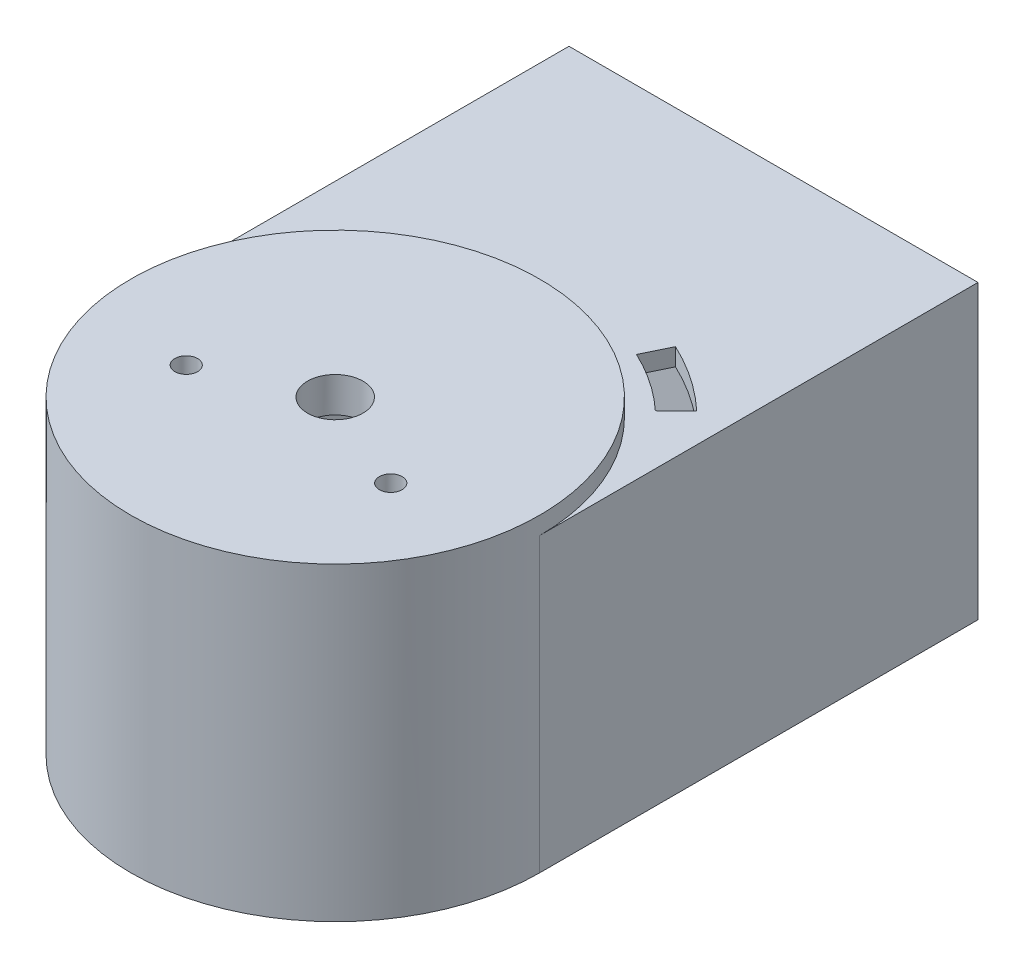
SolidWorks part; units mm, degrees
ref_plane "Alzado" through (0, 0, 0) normal (0, 0, 1) x (1, 0, 0)
ref_plane "Planta" through (0, 0, 0) normal (0, 1, 0) x (1, 0, 0)
ref_plane "Vista lateral" through (0, 0, 0) normal (1, 0, 0) x (0, 0, -1)
sketch "Croquis1" plane through (0, 0, 0) normal (0, 1, 0) x (1, 0, 0)
  circle A0 centre (0, 0) radius 4.75
  circle A1 centre (0, 0) radius 35
  dimension "D1" = 9.5
  dimension "D2" = 70
extrude "Saliente-Extruir1" add sketch "Croquis1" along normal blind 0.0001 and the other way blind 3
sketch "Croquis2" plane through (0, -3, 0) normal (0, -1, 0) x (1, 0, 0)
  circle A0 centre (-17.5, 8) radius 1.95
  circle A1 centre (17.5, 8) radius 1.95
  dimension "D4" = 3.9
  dimension "D1" = 8
  dimension "D2" = 35
  dimension "D3" = 17.5
extrude "Cortar-Extruir1" cut sketch "Croquis2" against normal through all
sketch "Croquis10" plane through (0, -3, 0) normal (0, -1, 0) x (1, 0, 0)
  line L1 (-35, 0) -> (-35, -75)
  line L2 (35, 0) -> (35, -75)
  line L3 (-35, -75) -> (35, -75)
  arc A0 (35, 0) -> (-35, 0) centre (0, 0) ccw
  circle A1 centre (0, 0) radius 4.75
  circle A2 centre (-17.5, 8) radius 1.95
  circle A3 centre (17.5, 8) radius 1.95
extrude "Saliente-Extruir3" add sketch "Croquis10" along normal blind 50
sketch "Croquis11" plane through (0, -53, 0) normal (0, -1, 0) x (1, 0, 0)
  line L1 (-32.0976, 0) -> (-32, -69.5)
  line L2 (32.0976, 0) -> (32, -69.5)
  line L3 (-29.5, -72) -> (29.5, -72)
  line L4 (-35, -75) -> (35, -75) construction
  line L5 (-35, 0) -> (-35, -75) construction
  arc A0 (32.0976, 0) -> (2.5013, 32) centre (0, 0) ccw
  arc A1 (32, -69.5) -> (29.5, -72) centre (32, -72) ccw
  arc A2 (-29.5, -72) -> (-32, -69.5) centre (-32, -72) ccw
  arc A3 (-2.5013, 32) -> (2.5013, 32) centre (0, 32) ccw
  arc A4 (-2.5013, 32) -> (-32.0976, 0) centre (0, 0) ccw
  circle A5 centre (32, -72) radius 1
  circle A6 centre (-32, -72) radius 1
  circle A7 centre (0, 32) radius 1
  arc A8 (35, 0) -> (-35, 0) centre (0, 0) ccw construction
  point P23 (0, 0)
extrude "Cortar-Extruir4" cut sketch "Croquis11" against normal blind 47
ref_plane "PlanoSoporte" through (0, 0, 0) normal (1, 0, 0) x (0, 0, -1)
sketch "Croquis18" plane through (0, -6, 0) normal (0, -1, 0) x (1, 0, 0)
  line L1 (2.4139, -42.4388) -> (-27.5861, -42.4388)
  line L2 (2.4139, -42.4388) -> (2.4139, -68.9388)
  line L3 (2.4139, -68.9388) -> (-27.5861, -68.9388)
  line L4 (-27.5861, -42.4388) -> (-27.5861, -68.9388)
  line L5 (2.4139, -42.4388) -> (-27.5861, -68.9388) construction
  line L6 (2.4139, -68.9388) -> (-27.5861, -42.4388) construction
  line L7 (-27.5861, -36.9388) -> (2.4139, -36.9388)
  line L8 (-27.5861, -36.9388) -> (-27.5861, -10.4388)
  line L9 (-27.5861, -10.4388) -> (2.4139, -10.4388)
  line L10 (2.4139, -36.9388) -> (2.4139, -10.4388)
  line L11 (-27.5861, -36.9388) -> (2.4139, -10.4388) construction
  line L12 (-27.5861, -10.4388) -> (2.4139, -36.9388) construction
  circle A0 centre (-27.5861, -42.4388) radius 2.5
  circle A1 centre (2.4139, -42.4388) radius 2.5
  circle A2 centre (2.4139, -68.9388) radius 2.5
  circle A3 centre (-27.5861, -68.9388) radius 2.5
  circle A4 centre (-27.5861, -42.4388) radius 1.5
  circle A5 centre (2.4139, -42.4388) radius 1.5
  circle A6 centre (2.4139, -68.9388) radius 1.5
  circle A7 centre (-27.5861, -68.9388) radius 1.5
  circle A8 centre (-27.5861, -36.9388) radius 2.5
  circle A9 centre (2.4139, -36.9388) radius 2.5
  circle A10 centre (2.4139, -10.4388) radius 2.5
  circle A11 centre (-27.5861, -10.4388) radius 2.5
  circle A12 centre (-27.5861, -36.9388) radius 1.5
  circle A13 centre (2.4139, -36.9388) radius 1.5
  circle A14 centre (2.4139, -10.4388) radius 1.5
  circle A15 centre (-27.5861, -10.4388) radius 1.5
  point P0 (-12.5861, -55.6888)
  point P13 (-12.5861, -23.6888)
  dimension "D3" = 30
  dimension "D1" = 30
  dimension "D2" = 26.5
  dimension "D4" = 26.5
  dimension "D5" = 0
  dimension "D6" = 32
extrude "Saliente-Extruir5" add sketch "Croquis18" along normal blind 5 contours A6 | A2 | A7 | A3 | A4 | A0 | A5 | A1 | A12 | A8 | A13 | A9 | A14 | A10 | A15 | A11
sketch "Croquis19" plane through (0, -3, 0) normal (0, 1, 0) x (1, 0, 0)
  line L0 (16.4482, 35.1007) -> (18.6276, 39.6011)
  line L1 (29.9998, 31.8629) -> (26.4088, 28.3756)
  arc A0 (18.6276, 39.6011) -> (29.9998, 31.8629) centre (0, 0) cw
  arc A1 (16.4482, 35.1007) -> (26.4088, 28.3756) centre (0, 0) cw
  dimension "D1" = 5
  dimension "D2" = 20
extrude "Cortar-Extruir6" cut sketch "Croquis19" against normal blind 3
